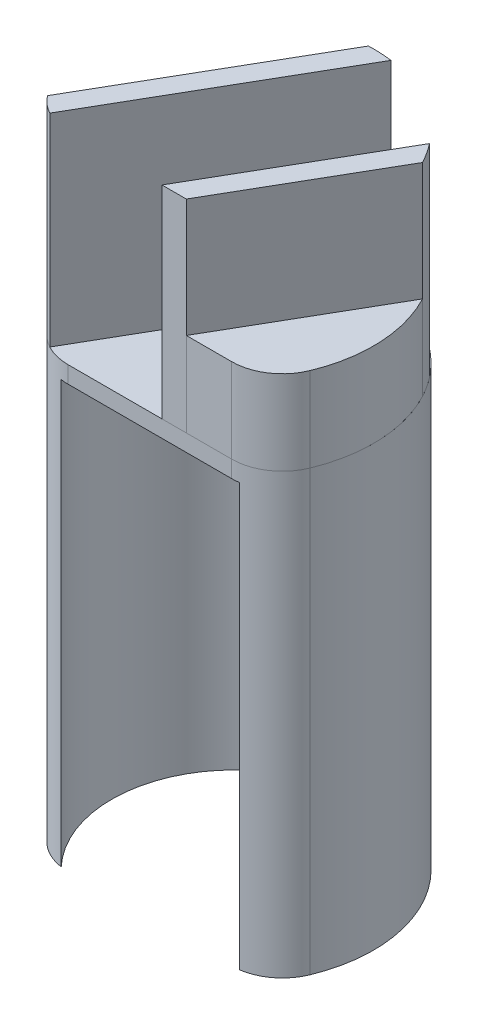
SolidWorks part; units mm, degrees
ref_plane "前视基准面" through (0, 0, 0) normal (0, 0, 1) x (1, 0, 0)
ref_plane "上视基准面" through (0, 0, 0) normal (0, 1, 0) x (1, 0, 0)
ref_plane "右视基准面" through (0, 0, 0) normal (1, 0, 0) x (0, 0, -1)
other "Configuration Table"
sketch "草图1" plane through (0, 0, 0) normal (0, 1, 0) x (1, 0, 0)
  circle A0 centre (0, 0) radius 14.5
  circle A1 centre (0, 0) radius 16.5
  dimension "D1" = 29
  dimension "D2" = 2
extrude "凸台-拉伸1" add sketch "草图1" along normal blind 35
sketch "草图3" plane through (0, 35, 0) normal (0, 1, 0) x (1, 0, 0)
  circle A1 centre (0, 0) radius 16.5
  circle A2 centre (0, 0) radius 16.5
  dimension "D1" = 0
extrude "凸台-拉伸2" add sketch "草图3" along normal blind 2
ref_plane "基准面1" through (0, 0, 10) normal (0, 0, 1) x (1, 0, 0)
sketch "草图4" plane through (0, 0, 10) normal (0, 0, 1) x (1, 0, 0)
  line L1 (-49.9355, 39.7218) -> (28.4145, 39.7218)
  line L2 (-49.9355, 39.7218) -> (-49.9355, -52.0807)
  line L3 (-49.9355, -52.0807) -> (28.4145, -52.0807)
  line L4 (28.4145, 39.7218) -> (28.4145, -52.0807)
extrude "切除-拉伸1" cut sketch "草图4" along normal through all
sketch "草图5" plane through (0, 37, 0) normal (0, 1, 0) x (1, 0, 0)
  circle A0 centre (0, 0) radius 3.75
  dimension "D1" = 7.5
extrude "切除-拉伸2" cut sketch "草图5" against normal up to next
fillet "圆角1" radius 6 2 edges at (-13.1244, 18.5, 10) (13.1244, 18.5, 10)
sketch "草图6" plane through (0, 37, 0) normal (0, 1, 0) x (1, 0, 0)
  line L0 (13.0479, 10.0996) -> (1.4434, -10)
  line L1 (-0.5833, 16.4897) -> (-14.4988, -7.6126)
  line L2 (-24.0688, -10) -> (24.0688, -10) construction
  line L3 (2.2226, 16.3496) -> (-12.5707, -9.2732)
  line L4 (14.5721, 7.7397) -> (4.3301, -10)
  line L5 (-9.7082, -10) -> (9.7082, -10) construction
  line L7 (-9.7082, -10) -> (9.7082, -10)
  line L8 (1.4434, -10) -> (4.3301, -10)
  circle A0 centre (0, 0) radius 6.25 construction
  arc A1 (-15.2558, -6.2857) -> (-9.7082, -10) centre (-9.7082, -4) ccw construction
  arc A2 (15.2558, -6.2857) -> (-15.2558, -6.2857) centre (0, 0) ccw construction
  arc A3 (2.2226, 16.3496) -> (-0.5833, 16.4897) centre (0, 0) ccw
  arc A6 (15.2558, -6.2857) -> (-15.2558, -6.2857) centre (0, 0) ccw
  arc A7 (-15.2558, -6.2857) -> (-9.7082, -10) centre (-9.7082, -4) ccw
  arc A8 (9.7082, -10) -> (15.2558, -6.2857) centre (9.7082, -4) ccw
  arc A9 (14.5721, 7.7397) -> (13.0479, 10.0996) centre (0, 0) ccw
  arc A10 (-14.4988, -7.6126) -> (-12.5707, -9.2732) centre (-9.7082, -4) ccw
  dimension "D1" = 12.5
  dimension "D2" = 60
  dimension "D3" = 2.5
  dimension "D4" = 2.5
  dimension "D5" = 0
extrude "凸台-拉伸3" add sketch "草图6" along normal blind 24 separate body
sketch "草图9" plane through (0, 37, 0) normal (0, 1, 0) x (1, 0, 0)
  line L0 (4.3301, -10) -> (14.5721, 7.7397) construction
  line L1 (-9.7082, -10) -> (9.7082, -10)
  line L2 (4.3301, -10) -> (9.7082, -10)
  line L3 (4.3301, -10) -> (14.5721, 7.7397)
  arc A3 (15.2558, -6.2857) -> (-15.2558, -6.2857) centre (0, 0) ccw
  arc A4 (-15.2558, -6.2857) -> (-9.7082, -10) centre (-9.7082, -4) ccw
  arc A5 (9.7082, -10) -> (15.2558, -6.2857) centre (9.7082, -4) ccw
  arc A6 (15.2558, -6.2857) -> (14.5721, 7.7397) centre (0, 0) ccw
  arc A8 (9.7082, -10) -> (15.2558, -6.2857) centre (9.7082, -4) ccw
  dimension "D1" = 0
extrude "凸台-拉伸7" add sketch "草图9" along normal blind 10 separate body
sketch "草图10" plane through (0, 0, 0) normal (0, -1, 0) x (1, 0, 0)
  arc A4 (-10.5572, 9.9396) -> (10.5572, 9.9396) centre (0, 0) ccw
  arc A6 (-15.2558, 6.2857) -> (15.2558, 6.2857) centre (0, 0) ccw
  arc A10 (-15.2558, 6.2857) -> (15.2558, 6.2857) centre (0, 0) ccw
  arc A13 (-10.5572, 9.9396) -> (10.5572, 9.9396) centre (0, 0) ccw
  arc A16 (-10.5572, 9.9396) -> (-15.2558, 6.2857) centre (-9.7082, 4) ccw
  arc A18 (-10.5572, 9.9396) -> (-15.2558, 6.2857) centre (-9.7082, 4) ccw
  arc A19 (15.2558, 6.2857) -> (10.5572, 9.9396) centre (9.7082, 4) ccw
  arc A20 (15.2558, 6.2857) -> (10.5572, 9.9396) centre (9.7082, 4) ccw
  dimension "D1" = 0
extrude "凸台-拉伸8" add sketch "草图10" along normal blind 15
